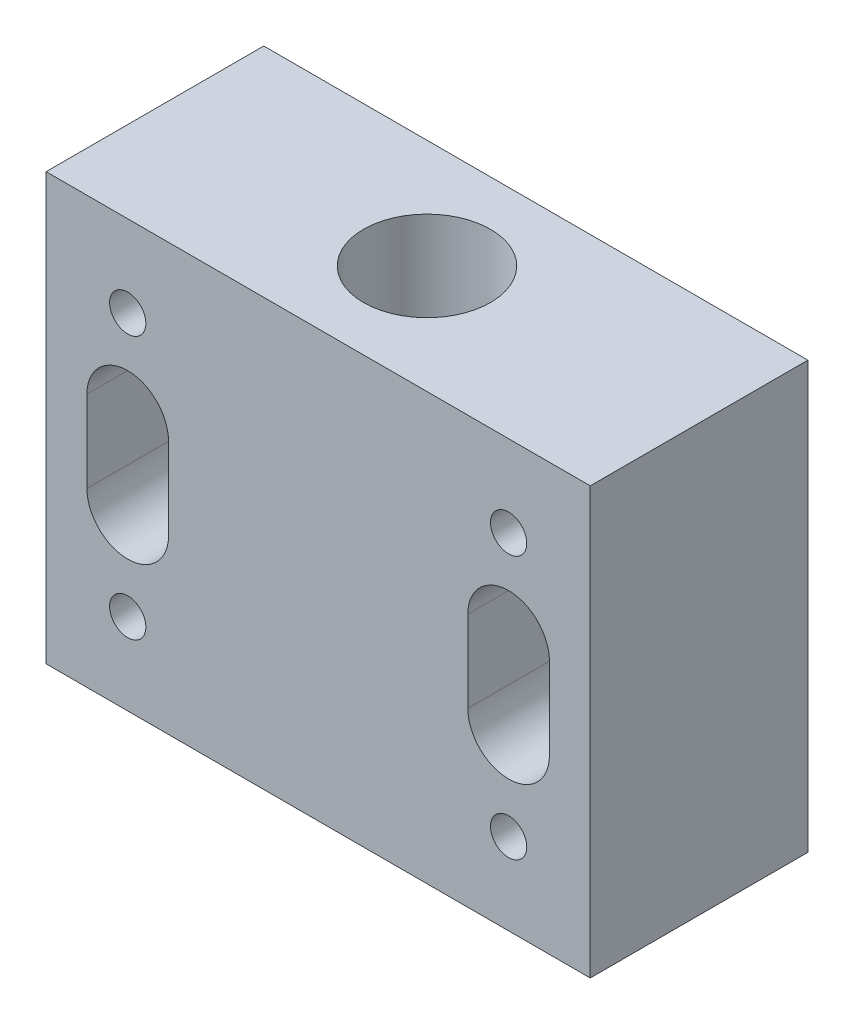
SolidWorks part; units mm, degrees
ref_plane "Front Plane" through (0, 0, 0) normal (0, 0, 1) x (1, 0, 0)
ref_plane "Top Plane" through (0, 0, 0) normal (0, 1, 0) x (1, 0, 0)
ref_plane "Right Plane" through (0, 0, 0) normal (1, 0, 0) x (0, 0, -1)
sketch "Sketch2" plane through (0, 0, 0) normal (0, 1, 0) x (1, 0, 0)
  line L1 (-30, -12) -> (30, -12)
  line L2 (-30, -12) -> (-30, 12)
  line L3 (-30, 12) -> (30, 12)
  line L4 (30, -12) -> (30, 12)
  line L5 (-30, -12) -> (30, 12) construction
  line L6 (-30, 12) -> (30, -12) construction
  circle A0 centre (0, 0) radius 7
  point P0 (0, 0)
  dimension "D3" = 14
  dimension "D1" = 60
  dimension "D2" = 24
extrude "Boss-Extrude1" add sketch "Sketch2" along normal blind 47
sketch "Sketch7" plane through (0, 47, 0) normal (0, 1, 0) x (1, 0, 0)
extrude "Boss-Extrude2" add sketch "Sketch2<2>" along normal blind 25.5
sketch "Sketch2<2>" plane through (0, 0, 0) normal (0, 1, 0) x (1, 0, 0) same geometry as "Sketch2"
sketch "Sketch8" plane through (0, 0, 12) normal (0, 0, 1) x (1, 0, 0)
  line L0 (-21, 9) -> (21, 9) construction
  line L1 (21, 9) -> (21, 38) construction
  line L2 (21, 38) -> (-21, 38) construction
  line L3 (-21, 38) -> (-21, 9) construction
  circle A0 centre (-21, 9) radius 2
  circle A1 centre (-21, 38) radius 2
  circle A2 centre (21, 38) radius 2
  circle A3 centre (21, 9) radius 2
  dimension "D1" = 4
extrude "Cut-Extrude1" cut sketch "Sketch8" against normal through all
sketch "Sketch9" plane through (0, 0, 12) normal (0, 0, 1) x (1, 0, 0)
  line L0 (-21, 47) -> (-21, 0) construction
  line L1 (-30, 47) -> (30, 47) construction
  line L2 (-30, 0) -> (30, 0) construction
  line L3 (-21, 36) -> (-21, 11) construction
  line L4 (21, 36) -> (21, 11) construction
  line L5 (21, 47) -> (21, 0) construction
  line L6 (-21, 19) -> (-21, 28) construction
  line L8 (-25.5, 19) -> (-25.5, 28)
  line L9 (-16.5, 19) -> (-16.5, 28)
  line L11 (0, 47) -> (0, 0) construction
  line L12 (21, 36) -> (21, 11) construction
  line L13 (21, 19) -> (21, 28) construction
  line L14 (25.5, 19) -> (25.5, 28)
  line L15 (16.5, 19) -> (16.5, 28)
  circle A2 centre (-21, 38) radius 2 construction
  circle A3 centre (-21, 9) radius 2 construction
  circle A4 centre (21, 38) radius 2 construction
  circle A5 centre (21, 9) radius 2 construction
  arc A6 (-25.5, 19) -> (-16.5, 19) centre (-21, 19) ccw
  arc A7 (-16.5, 28) -> (-25.5, 28) centre (-21, 28) ccw
  arc A8 (25.5, 19) -> (16.5, 19) centre (21, 19) cw
  arc A9 (16.5, 28) -> (25.5, 28) centre (21, 28) cw
  point P24 (-21, 23.5)
  point P34 (21, 23.5)
  dimension "D1" = 9
  dimension "D2" = 9
extrude "Cut-Extrude2" cut sketch "Sketch9" against normal through all
sketch "Sketch10" plane through (0, 0, -12) normal (0, 0, -1) x (-1, 0, 0)
  circle A0 centre (14.2, 42.5) radius 2
  circle A1 centre (14.2, 4.5) radius 2
  circle A2 centre (-15.8, 4.5) radius 2
  circle A3 centre (-15.8, 42.5) radius 2
  dimension "D1" = 4
extrude "Cut-Extrude3" cut sketch "Sketch10" against normal blind 10
